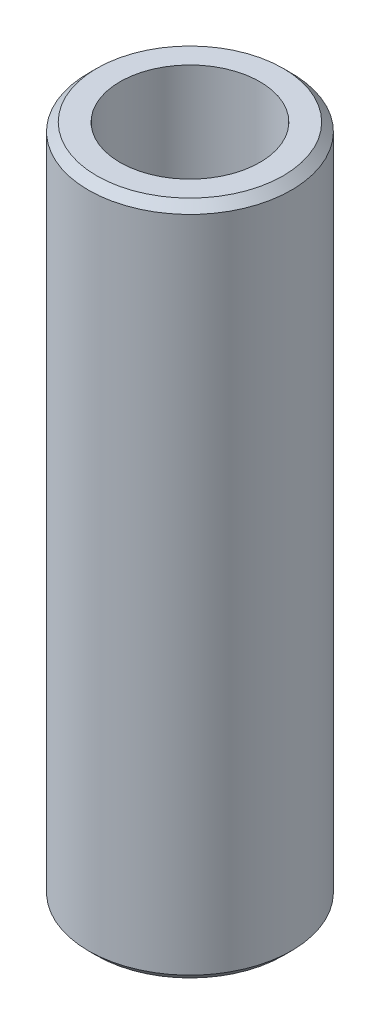
SolidWorks part; units mm, degrees
ref_plane "Front Plane" through (0, 0, 0) normal (0, 0, 1) x (1, 0, 0)
ref_plane "Top Plane" through (0, 0, 0) normal (0, 1, 0) x (1, 0, 0)
ref_plane "Right Plane" through (0, 0, 0) normal (1, 0, 0) x (0, 0, -1)
sketch "Sketch1" plane through (0, 0, 0) normal (0, 1, 0) x (1, 0, 0)
  circle A0 centre (0, 0) radius 12.5
  dimension "SHAFT_OD" = 25
extrude "Boss-Extrude1" add sketch "Sketch1" along normal blind 83.2252
sketch "Sketch2" plane through (0, 0, 0) normal (0, 1, 0) x (1, 0, 0)
  circle A0 centre (0, 0) radius 8.6207
  dimension "BORE_D" = 17.2414
extrude "Cut-Extrude1" cut sketch "Sketch2" along normal through all
chamfer "Chamfer1" distance 1.0208 angle 45 2 edges at (0, 83.2252, 12.5) (0, 0, 12.5)
